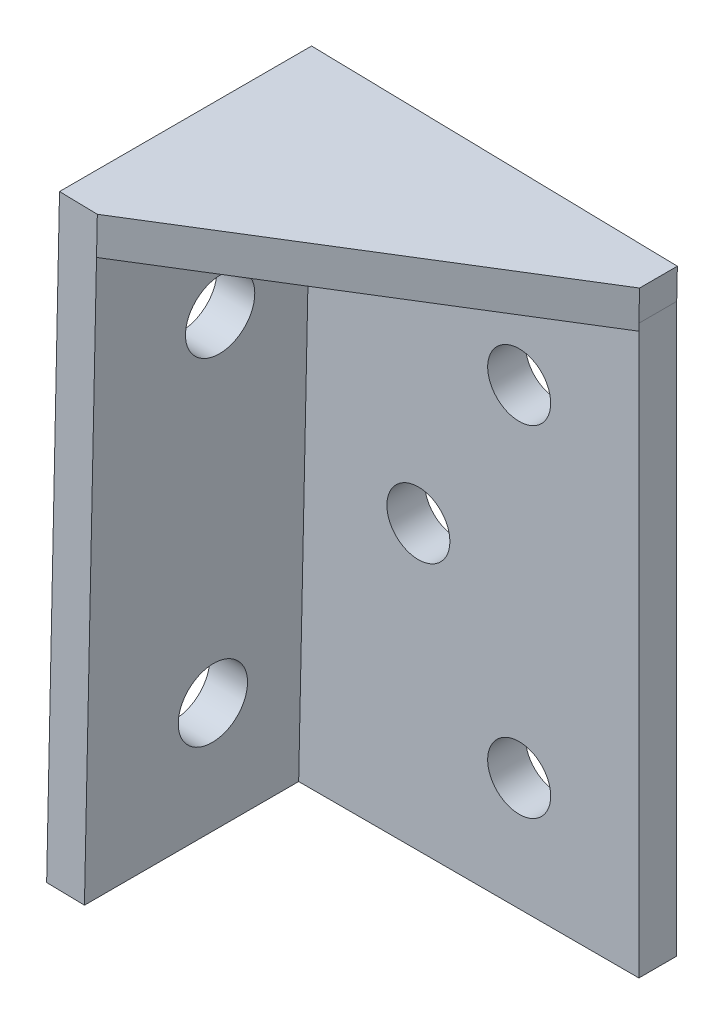
SolidWorks part; units mm, degrees
ref_plane "Front Plane" through (0, 0, 0) normal (0, 0, 1) x (1, 0, 0)
ref_plane "Top Plane" through (0, 0, 0) normal (0, 1, 0) x (1, 0, 0)
ref_plane "Right Plane" through (0, 0, 0) normal (1, 0, 0) x (0, 0, -1)
sketch "Sketch1" plane through (0, 0, 0) normal (0, 0, 1) x (1, 0, 0)
  line L0 (0, 0) -> (0.9583, 45)
  line L1 (0.9583, 45) -> (27, 45)
  line L2 (27, 45) -> (27, 0)
  line L3 (27, 0) -> (0, 0)
  line L4 (27, 22.5) -> (9.5, 22.5) construction
  line L5 (17.5, 9) -> (17.5, 36) construction
  circle A0 centre (17.5, 36) radius 2.5
  circle A1 centre (17.5, 9) radius 2.5
  circle A2 centre (9.5, 22.5) radius 2.5
  circle A3 centre (17.5, 36) radius 6 construction
  circle A4 centre (9.5, 22.5) radius 6 construction
  circle A5 centre (17.5, 9) radius 6 construction
  point P9 (17.5, 22.5)
  dimension "D2" = 5
  dimension "D4" = 12
  dimension "D1" = 91.22
  dimension "D3" = 45
  dimension "D5" = 27
  dimension "D6" = 27
  dimension "D7" = 9.5
  dimension "D8" = 17.5
extrude "Boss-Extrude1" add sketch "Sketch1" along normal blind 3
sketch "Sketch2" plane through (0, 0, 0) normal (-0.9998, 0.0213, 0) x (0, 0, 1)
  line L0 (0, 45.0102) -> (20, 45.0102)
  line L1 (20, 45.0102) -> (20, 0)
  line L2 (20, 0) -> (0, 0)
  line L3 (0, 0) -> (0, 45.0102)
  line L5 (10, 45.0102) -> (10, 0) construction
  circle A0 centre (10, 36.0102) radius 2.75
  circle A1 centre (10, 9) radius 2.75
  point P3 (0, 0)
  point P14 (13, 36.3912)
  point P15 (13, 8.5315)
  dimension "D2" = 5.5
  dimension "D3" = 5.5
  dimension "D1" = 20
  dimension "D4" = 10
  dimension "D5" = 9
  dimension "D6" = 9
extrude "Boss-Extrude2" add sketch "Sketch2" along normal blind 3
sketch "Sketch3" plane through (0.9583, 45, 0) normal (0.0213, 0.9998, 0) x (0.9998, -0.0213, 0)
  line L0 (0, -20) -> (26.0358, -3)
  line L1 (26.0358, -3) -> (26.0358, 0)
  line L2 (26.0358, 0) -> (-3, 0)
  line L3 (-3, 0) -> (-3, -20)
  line L4 (-3, -20) -> (0, -20)
extrude "Boss-Extrude3" add sketch "Sketch3" along normal blind 3
